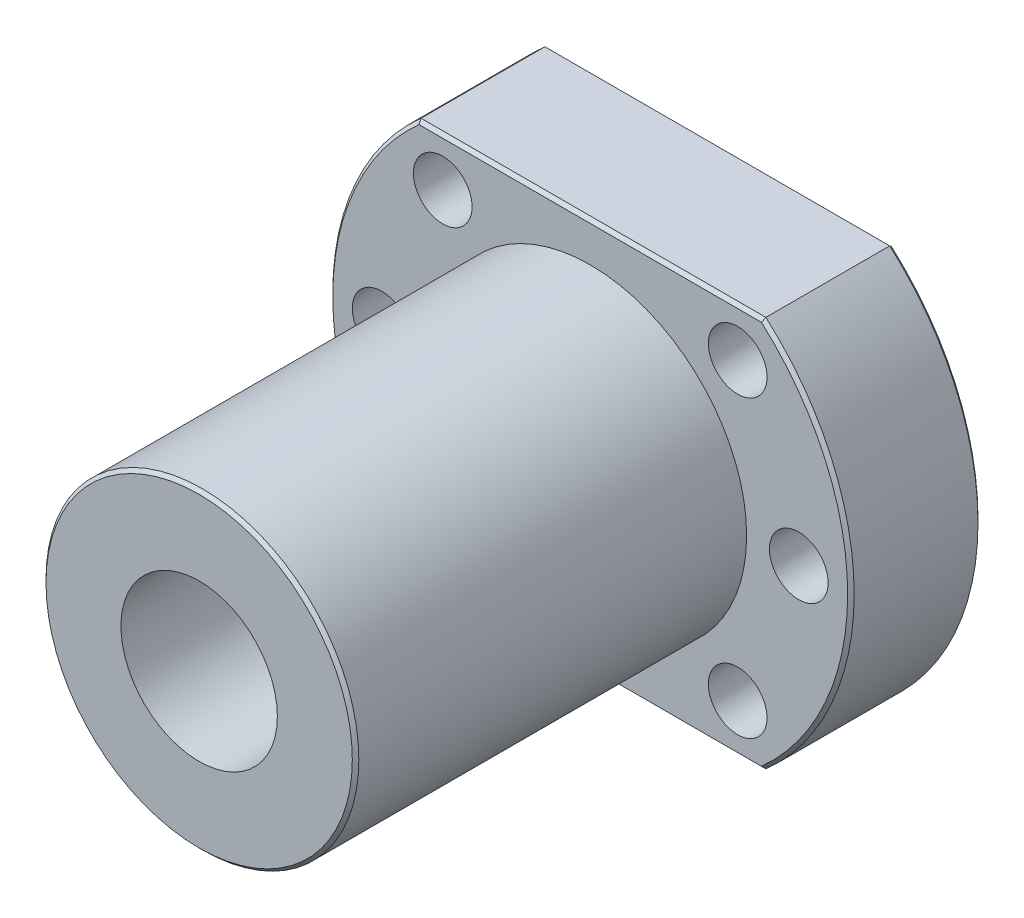
SolidWorks part; units mm, degrees
material "Alloy Steel"
ref_plane "Front Plane" through (0, 0, 0) normal (0, 0, 1) x (1, 0, 0)
ref_plane "Top Plane" through (0, 0, 0) normal (0, 1, 0) x (1, 0, 0)
ref_plane "Right Plane" through (0, 0, 0) normal (1, 0, 0) x (0, 0, -1)
sketch "Sketch1" plane through (0, 0, 0) normal (0, 0, 1) x (1, 0, 0)
  line L0 (-13.2288, 15) -> (13.2288, 15)
  line L1 (-20, 0) -> (20, 0) construction
  line L2 (-13.2288, -15) -> (13.2288, -15)
  arc A0 (-13.2288, 15) -> (-13.2288, -15) centre (0, 0) ccw
  arc A1 (13.2288, -15) -> (13.2288, 15) centre (0, 0) ccw
  circle A2 centre (0, 0) radius 16 construction
  circle A3 centre (-16, 0) radius 2.25
  circle A4 centre (-11.3137, 11.3137) radius 2.25
  circle A5 centre (0, 16) radius 2.25 construction
  circle A6 centre (11.3137, 11.3137) radius 2.25
  circle A7 centre (16, 0) radius 2.25
  circle A8 centre (11.3137, -11.3137) radius 2.25
  circle A9 centre (0, -16) radius 2.25 construction
  circle A10 centre (-11.3137, -11.3137) radius 2.25
  point P27 (0, 0)
  dimension "D1" = 40
  dimension "D3" = 32
  dimension "D5" = 4.5
  dimension "D2" = 15
  dimension "D4" = 8
extrude "Boss-Extrude1" add sketch "Sketch1" along normal blind 10
sketch "Sketch2" plane through (0, 0, 10) normal (0, 0, 1) x (1, 0, 0)
  circle A0 centre (0, 0) radius 12
  dimension "D1" = 24
extrude "Boss-Extrude2" add sketch "Sketch2" along normal blind 30
sketch "Sketch3" plane through (0, 0, 40) normal (0, 0, 1) x (1, 0, 0)
  circle A0 centre (0, 0) radius 6
  dimension "D1" = 12
extrude "Cut-Extrude1" cut sketch "Sketch3" against normal through all
chamfer "Chamfer1" distance 0.25 angle 45 9 edges at (0, -15, 0) (-20, 0, 0) (20, 0, 0) (0, 15, 0) (-20, 0, 10) (0, -15, 10) (20, 0, 10) (0, 15, 10) (12, 0, 40)
sketch "Sketch4" plane through (0, 0, 0) normal (0, 0, -1) x (-1, 0, 0)
  circle A0 centre (-11.3137, 11.3137) radius 3.5
  circle A1 centre (0, 16) radius 3.5 construction
  circle A2 centre (11.3137, 11.3137) radius 3.5
  circle A3 centre (16, 0) radius 3.5
  circle A4 centre (11.3137, -11.3137) radius 3.5
  circle A5 centre (0, -16) radius 3.5 construction
  circle A6 centre (-11.3137, -11.3137) radius 3.5
  circle A7 centre (-16, 0) radius 3.5
  point P19 (0, 0)
  dimension "D2" = 7
  dimension "D1" = 8
extrude "Cut-Extrude2" cut sketch "Sketch4" against normal blind 5
ref_axis "Axis1" through (0, 0, 0) along (0, 0, 1)
